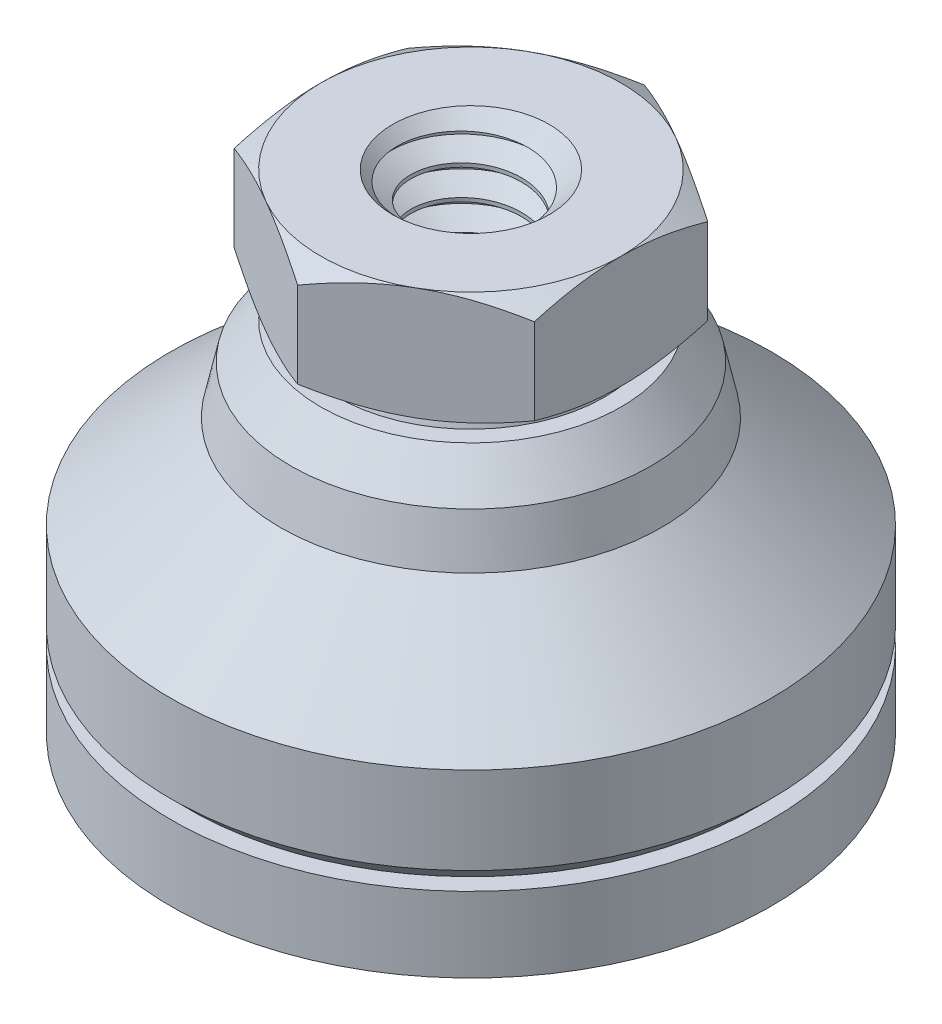
SolidWorks part; units mm, degrees
ref_plane "Front Plane" through (0, 0, 0) normal (0, 0, 1) x (1, 0, 0)
ref_plane "Top Plane" through (0, 0, 0) normal (0, 1, 0) x (1, 0, 0)
ref_plane "Right Plane" through (0, 0, 0) normal (1, 0, 0) x (0, 0, -1)
sketch "Sketch1" plane through (0, 0, 0) normal (0, 0, 1) x (1, 0, 0)
  line L0 (0, 0) -> (0, 20.6375) construction
  line L1 (-12.7, 0) -> (12.7, 0) construction
  line L2 (-3.175, 20.6375) -> (3.175, 20.6375) construction
  line L3 (-6.35, 15.875) -> (6.35, 15.875) construction
  point P7 (0, 12.7)
  point P10 (0, 15.875)
  point P11 (0, 3.175)
  point P12 (-6.35, 20.6375)
  dimension "D1" = 3.175
sketch "Sketch2" plane through (0, 0, 0) normal (0, 0, 1) x (1, 0, 0)
  line L0 (0, 3.175) -> (0, 7.747)
  line L1 (0, 0) -> (0, 20.6375) construction
  line L2 (-6.35, 15.113) -> (-5.6397, 15.113)
  line L3 (-6.35, 15.875) -> (-5.842, 15.875) construction
  line L4 (-6.35, 15.113) -> (-7.62, 13.589)
  line L5 (-8.0645, 11.557) -> (-12.7, 7.62)
  line L6 (-12.7, 7.62) -> (-12.7, 3.937)
  line L7 (-11.938, 3.175) -> (0, 3.175)
  line L8 (-12.7, 0) -> (-12.7, 3.175) construction
  line L9 (-7.62, 13.589) -> (-8.0645, 11.557)
  line L10 (0, 15.875) -> (0, 20.6375) construction
  line L11 (-3.175, 20.6375) -> (3.175, 20.6375) construction
  line L12 (-5.842, 15.875) -> (-5.842, 13.589) construction
  line L13 (-7.62, 13.589) -> (0, 13.589) construction
  line L14 (-12.7, 3.937) -> (-11.938, 3.175)
  line L15 (-12.7, 3.937) -> (-12.7, 3.175) construction
  line L16 (-12.7, 3.175) -> (-11.938, 3.175) construction
  arc A0 (-5.6397, 15.113) -> (0, 7.747) centre (0, 13.589) ccw
  dimension "D1" = 16.129
  dimension "D2" = 15.24
  dimension "D3" = 12.7
  dimension "H2" = 3.937
  dimension "D4" = 0.508
  dimension "H1" = 4.445
  dimension "C1" = 0.762
  dimension "H3" = 2.032
  dimension "H4" = 1.524
revolve "Revolve1" add sketch "Sketch2" angle 360 about L0
sketch "Sketch10" plane through (0, 0, 0) normal (0, 0, 1) x (1, 0, 0)
  line L0 (0, 15.875) -> (-5.3762, 15.875)
  line L1 (0, 7.747) -> (0, 15.875)
  arc A0 (-5.3762, 15.875) -> (0, 7.747) centre (0, 13.589) ccw
  arc A1 (-5.6397, 15.113) -> (0, 7.747) centre (0, 13.589) ccw construction
revolve "Revolve2" add sketch "Sketch10" angle 360 about L1
sketch "Sketch3" plane through (0, 15.875, 0) normal (0, 1, 0) x (1, 0, 0)
  line L1 (0, 7.3323) -> (-6.35, 3.6662)
  line L2 (-6.35, 3.6662) -> (-6.35, -3.6662)
  line L3 (-6.35, -3.6662) -> (0, -7.3323)
  line L4 (0, -7.3323) -> (6.35, -3.6662)
  line L5 (6.35, -3.6662) -> (6.35, 3.6662)
  line L6 (6.35, 3.6662) -> (0, 7.3323)
  circle A0 centre (0, 0) radius 6.35 construction
extrude "Boss-Extrude1" add sketch "Sketch3" along normal up to vertex (4.7625 mm away) up to point (0, 20.6375, 0)
sketch "Sketch4" plane through (0, 0, 0) normal (1, 0, 0) x (0, 0, -1)
  line L0 (-8.3147, 20.6375) -> (-8.3147, 15.875)
  line L1 (-8.3147, 15.875) -> (-6.35, 15.875)
  line L2 (-6.35, 15.875) -> (-7.3323, 16.4422)
  line L3 (-7.3323, 16.4422) -> (-7.3323, 20.0703)
  line L4 (-7.3323, 20.0703) -> (-6.35, 20.6375)
  line L5 (-6.35, 20.6375) -> (-8.3147, 20.6375)
  line L9 (-7.3323, 20.6375) -> (-7.3323, 15.875) construction
  dimension "D1" = 30
revolve "Cut-Revolve2" cut sketch "Sketch4" angle 360 about L0
sketch "Sketch5" plane through (0, 20.6375, 0) normal (0, 1, 0) x (1, 0, 0)
  circle A0 centre (0, 0) radius 3.175
extrude "Cut-Extrude1" cut sketch "Sketch5" against normal up to vertex (7.9375 mm away) up to point (0, 12.7, 0)
sketch "Sketch6" plane through (0, 20.6375, 0) normal (0, 1, 0) x (1, 0, 0)
  circle A0 centre (0, 0) radius 3.175 construction
  circle A1 centre (0, 0) radius 3.175
  point P5 (3.175, 0)
curve "Helix/Spiral1" pitch 1.27 height 9.2075 turns 7.25 parameters "Pitch"=1.27
sketch "Sketch7" plane through (0, 0, 0) normal (0, 0, 1) x (1, 0, 0)
  line L0 (3.3125, 21.8281) -> (3.3125, 20.5581) construction
  line L1 (3.3125, 20.5581) -> (2.2126, 21.1931) construction
  line L2 (2.2126, 21.1931) -> (3.3125, 21.8281) construction
  line L3 (2.3501, 21.2725) -> (2.3501, 21.1137) construction
  line L4 (3.175, 21.7487) -> (3.175, 20.6375) construction
  line L5 (2.2126, 21.1931) -> (2.3501, 21.1931) construction
  line L6 (3.175, 21.1931) -> (3.3125, 21.1931) construction
  line L7 (3.2437, 21.7884) -> (2.3501, 21.2725)
  line L8 (2.3501, 21.2725) -> (2.3501, 21.1137)
  line L9 (2.3501, 21.1137) -> (3.2437, 20.5978)
  line L10 (3.2437, 20.5978) -> (3.2437, 21.7884)
  point P11 (3.2437, 21.1931)
  dimension "D1" = 1.27
  dimension "D2" = 0.1588
sketch "Sketch8" plane through (0, 20.6375, 0) normal (0, 1, 0) x (1, 0, 0)
  line L0 (0, 0) -> (-1.6562, 2.8687) construction
  line L1 (-3.175, 5.4993) -> (-6.35, 3.6662) construction
  circle A0 centre (0, 0) radius 3.3125
sweep "Sweep1" add profiles "Sketch7" path "Helix/Spiral1"
extrude "Cut-Extrude2" cut sketch "Sketch8" against normal up to vertex (7.9375 mm away) draft 45 and the other way through all draft 45
sketch "SketchX" plane through (0, 0, 0) normal (0, 0, 1) x (1, 0, 0)
  line L0 (0, 13.589) -> (-2.9403, 35.9229)
  line L1 (0, 13.589) -> (2.9403, 35.9229)
  line L2 (0, 0) -> (0, 20.6375) construction
  line L3 (0, 13.589) -> (0, 36.1156)
  line L4 (3.175, 20.6375) -> (-3.175, 20.6375) construction
  line L5 (-3.175, 20.6375) -> (-3.175, 12.7)
  line L6 (3.175, 20.6375) -> (3.175, 12.7)
  line L7 (3.175, 12.7) -> (-3.175, 12.7)
  arc A0 (-2.9403, 35.9229) -> (2.9403, 35.9229) centre (0, 13.589) cw construction
  dimension "D1" = 7.5
  dimension "D2" = 15.4781
sketch "Sketch11" plane through (0, 0, 0) normal (0, 0, 1) x (1, 0, 0)
  line L1 (0, 0) -> (12.7, 0)
  line L2 (0, 0) -> (0, 3.175)
  line L3 (0, 3.175) -> (12.7, 3.175)
  line L4 (12.7, 0) -> (12.7, 3.175)
  point P6 (12.7, 1.5875)
revolve "Revolve3" add sketch "Sketch11" angle 360 about L2
equation "\"D3@Helix/Spiral1\" = \"Pitch@Helix/Spiral1\" + \"Thread Dp.@Sketch1\""
equation "\"D1@Sketch7\" = \"Pitch@Helix/Spiral1\" "
equation "\"D2@Sketch7\" = \"D1@Sketch7\" / 8"
equation "\"D2@SketchX\" = \"Overall Ht.@Sketch1\" * 0.75"
